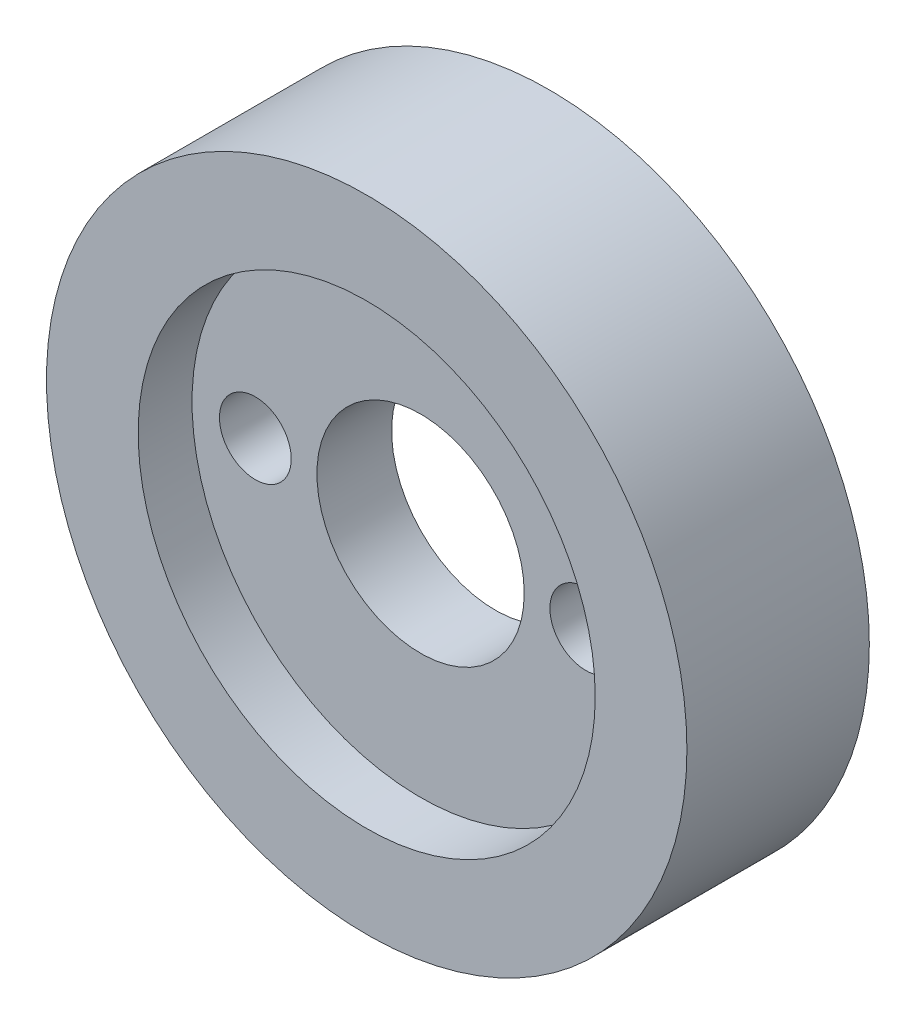
SolidWorks part; units mm, degrees
ref_plane "Front Plane" through (0, 0, 0) normal (0, 0, 1) x (1, 0, 0)
ref_plane "Top Plane" through (0, 0, 0) normal (0, 1, 0) x (1, 0, 0)
ref_plane "Right Plane" through (0, 0, 0) normal (1, 0, 0) x (0, 0, -1)
sketch "Sketch1" plane through (0, 0, 0) normal (0, 0, 1) x (1, 0, 0)
  circle A0 centre (0, 0) radius 9.8091
  circle A1 centre (0, 0) radius 3.175
  dimension "D1" = 19.6182
  dimension "D2" = 6.35
extrude "Boss-Extrude1" add sketch "Sketch1" along normal mid plane 5.588
sketch "Sketch2" plane through (0, 0, 2.794) normal (0, 0, 1) x (1, 0, 0)
  line L0 (0, 0) -> (0, 1.2313) construction
  line L1 (-7, 0) -> (-3.075, 0)
  circle A0 centre (0, 0) radius 7
  circle A1 centre (0, 0) radius 3.075
  circle A2 centre (-5.061, 0) radius 1.1
  circle A3 centre (5.061, 0) radius 1.1
  circle M2 centre (0, 0) radius 3.175
  dimension "D1" = 14
  dimension "D2" = 6.15
  dimension "D3" = 2.2
  dimension "D4" = 10.1219
extrude "Cut-Extrude1" cut sketch "Sketch2" against normal blind 1.65 contours A2 A0 A3 M2 region at (0, 6.802, 2.794)
mirror "Mirror1" about plane through (0, 0, 0) normal (0, 0, 1) of "Cut-Extrude1"
extrude "Cut-Extrude2" cut sketch "Sketch2<3>" against normal through all contours L1 A2 | L1 A2 | A3 region at (-5.061, -0.4669, 2.794) region at (-5.061, 0.4669, 2.794) region at (5.061, 0, 2.794)
sketch "Sketch2<3>" plane through (0, 0, 2.794) normal (0, 0, 1) x (1, 0, 0) same geometry as "Sketch2"
